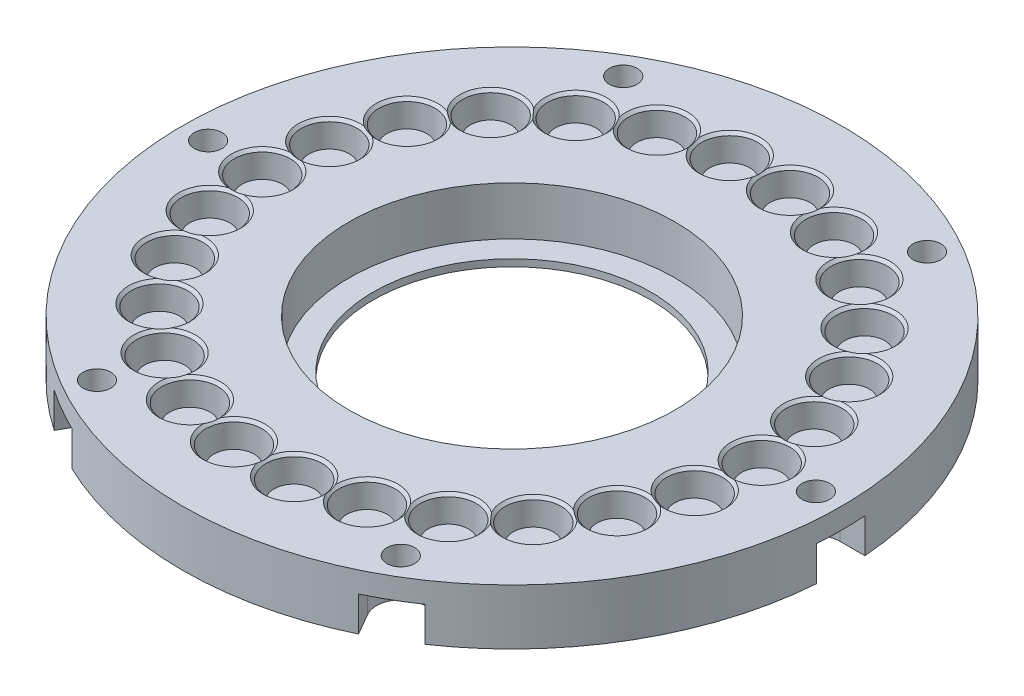
SolidWorks part; units mm, degrees
ref_plane "Front Plane" through (0, 0, 0) normal (0, 0, 1) x (1, 0, 0)
ref_plane "Top Plane" through (0, 0, 0) normal (0, 1, 0) x (1, 0, 0)
ref_plane "Right Plane" through (0, 0, 0) normal (1, 0, 0) x (0, 0, -1)
sketch "Sketch1" plane through (0, 0, 0) normal (0, 1, 0) x (1, 0, 0)
  circle A0 centre (0, 0) radius 47.5
  circle A1 centre (0, 0) radius 36 construction
  circle A2 centre (36, 0) radius 4.05
  circle A3 centre (34.9539, -8.6154) radius 4.05
  circle A4 centre (31.8764, -16.73) radius 4.05
  circle A5 centre (26.9464, -23.8724) radius 4.05
  circle A6 centre (20.4503, -29.6274) radius 4.05
  circle A7 centre (12.7658, -33.6606) radius 4.05
  circle A8 centre (4.3393, -35.7375) radius 4.05
  circle A9 centre (-4.3393, -35.7375) radius 4.05
  circle A10 centre (-12.7658, -33.6606) radius 4.05
  circle A11 centre (-20.4503, -29.6274) radius 4.05
  circle A12 centre (-26.9464, -23.8724) radius 4.05
  circle A13 centre (-31.8764, -16.73) radius 4.05
  circle A14 centre (-34.9539, -8.6154) radius 4.05
  circle A15 centre (-36, 0) radius 4.05
  circle A16 centre (-34.9539, 8.6154) radius 4.05
  circle A17 centre (-31.8764, 16.73) radius 4.05
  circle A18 centre (-26.9464, 23.8724) radius 4.05
  circle A19 centre (-20.4503, 29.6274) radius 4.05
  circle A20 centre (-12.7658, 33.6606) radius 4.05
  circle A21 centre (-4.3393, 35.7375) radius 4.05
  circle A22 centre (4.3393, 35.7375) radius 4.05
  circle A23 centre (12.7658, 33.6606) radius 4.05
  circle A24 centre (20.4503, 29.6274) radius 4.05
  circle A25 centre (26.9464, 23.8724) radius 4.05
  circle A26 centre (31.8764, 16.73) radius 4.05
  circle A27 centre (34.9539, 8.6154) radius 4.05
  point P58 (0, 0)
  dimension "D1" = 95
  dimension "D2" = 72
  dimension "D3" = 8.1
  dimension "D4" = 26
extrude "Boss-Extrude1" add sketch "Sketch1" along normal blind 5
sketch "Sketch2" plane through (0, 0, 0) normal (0, -1, 0) x (1, 0, 0)
  circle A1 centre (0, 0) radius 47.5
  circle A2 centre (0, 0) radius 47.5
  dimension "D1" = 0
extrude "Boss-Extrude2" add sketch "Sketch2" along normal blind 3
sketch "Sketch3" plane through (0, 0, 0) normal (0, 1, 0) x (1, 0, 0)
  circle A0 centre (36, 0) radius 2.9
  circle A1 centre (34.9539, -8.6154) radius 2.9
  circle A2 centre (31.8764, -16.73) radius 2.9
  circle A3 centre (26.9464, -23.8724) radius 2.9
  circle A4 centre (20.4503, -29.6274) radius 2.9
  circle A5 centre (12.7658, -33.6606) radius 2.9
  circle A6 centre (4.3393, -35.7375) radius 2.9
  circle A7 centre (-4.3393, -35.7375) radius 2.9
  circle A8 centre (-12.7658, -33.6606) radius 2.9
  circle A9 centre (-20.4503, -29.6274) radius 2.9
  circle A10 centre (-26.9464, -23.8724) radius 2.9
  circle A11 centre (-31.8764, -16.73) radius 2.9
  circle A12 centre (-34.9539, -8.6154) radius 2.9
  circle A13 centre (-36, 0) radius 2.9
  circle A14 centre (-34.9539, 8.6154) radius 2.9
  circle A15 centre (-31.8764, 16.73) radius 2.9
  circle A16 centre (-26.9464, 23.8724) radius 2.9
  circle A17 centre (-20.4503, 29.6274) radius 2.9
  circle A18 centre (-12.7658, 33.6606) radius 2.9
  circle A19 centre (-4.3393, 35.7375) radius 2.9
  circle A20 centre (4.3393, 35.7375) radius 2.9
  circle A21 centre (12.7658, 33.6606) radius 2.9
  circle A22 centre (20.4503, 29.6274) radius 2.9
  circle A23 centre (26.9464, 23.8724) radius 2.9
  circle A24 centre (31.8764, 16.73) radius 2.9
  circle A25 centre (34.9539, 8.6154) radius 2.9
  point P55 (0, 0)
  dimension "D1" = 5.8
  dimension "D2" = 26
extrude "Boss-Extrude3" add sketch "Sketch3" along normal blind 2
sketch "Sketch5" plane through (0, 5, 0) normal (0, 1, 0) x (1, 0, 0)
  circle A0 centre (0, 0) radius 23.5
  dimension "D1" = 47
extrude "Cut-Extrude2" cut sketch "Sketch5" against normal blind 7
sketch "Sketch6" plane through (0, -2, 0) normal (0, 1, 0) x (1, 0, 0)
  circle A2 centre (0, 0) radius 20
  circle A3 centre (0, 0) radius 20
  dimension "D1" = 3.5
extrude "Cut-Extrude3" cut sketch "Sketch6" against normal up to next contours A3
sketch "Sketch7" plane through (0, -3, 0) normal (0, -1, 0) x (1, 0, 0)
  line L0 (43.8, 3.5) -> (47.3709, 3.5)
  line L1 (43.8, -3.5) -> (47.3709, -3.5)
  line L2 (24.9311, -36.1819) -> (26.7165, -39.2744)
  line L3 (18.8689, -39.6819) -> (20.6543, -42.7744)
  line L4 (-18.8689, -39.6819) -> (-20.6543, -42.7744)
  line L5 (-24.9311, -36.1819) -> (-26.7165, -39.2744)
  line L6 (-43.8, -3.5) -> (-47.3709, -3.5)
  line L7 (-43.8, 3.5) -> (-47.3709, 3.5)
  line L8 (-24.9311, 36.1819) -> (-26.7165, 39.2744)
  line L9 (-18.8689, 39.6819) -> (-20.6543, 42.7744)
  line L10 (18.8689, 39.6819) -> (20.6543, 42.7744)
  line L11 (24.9311, 36.1819) -> (26.7165, 39.2744)
  circle A0 centre (0, 0) radius 43.8 construction
  arc A1 (43.8, 3.5) -> (43.8, -3.5) centre (43.8, 0) ccw
  circle A2 centre (0, 0) radius 47.5 construction
  circle A3 centre (0, 0) radius 47.5
  arc A4 (24.9311, -36.1819) -> (18.8689, -39.6819) centre (21.9, -37.9319) ccw
  arc A5 (-18.8689, -39.6819) -> (-24.9311, -36.1819) centre (-21.9, -37.9319) ccw
  arc A6 (-43.8, -3.5) -> (-43.8, 3.5) centre (-43.8, 0) ccw
  arc A7 (-24.9311, 36.1819) -> (-18.8689, 39.6819) centre (-21.9, 37.9319) ccw
  arc A8 (18.8689, 39.6819) -> (24.9311, 36.1819) centre (21.9, 37.9319) ccw
  point P38 (0, 0)
  circle M5 centre (0, 0) radius 47.5
  dimension "D1" = 87.6
  dimension "D2" = 7
  dimension "D3" = 6
extrude "Cut-Extrude4" cut sketch "Sketch7" against normal blind 5 contours L8 A7 L9 M5 | L6 A6 L7 M5 | L10 A8 L11 M5 | L0 A1 L1 M5 | L2 A4 L3 M5 | L4 A5 L5 M5 region at (44.2065, -3, 0) region at (22.1033, -3, 38.284) region at (22.1033, -3, -38.284) region at (-22.1033, -3, 38.284) region at (-22.1033, -3, -38.284) region at (-44.2065, -3, 0)
sketch "Sketch8" plane through (0, 2, 0) normal (0, -1, 0) x (1, 0, 0)
  circle A0 centre (43.8, 0) radius 2
  circle A1 centre (21.9, -37.9319) radius 2
  circle A2 centre (-21.9, -37.9319) radius 2
  circle A3 centre (-43.8, 0) radius 2
  circle A4 centre (-21.9, 37.9319) radius 2
  circle A5 centre (21.9, 37.9319) radius 2
  point P16 (0, 0)
  dimension "D1" = 4
  dimension "D2" = 6
extrude "Cut-Extrude5" cut sketch "Sketch8" against normal through all
chamfer "Chamfer1" distance 0.4 angle 45 27 edges at (-20.4503, 5, -25.5774) (4.3393, 0, 39.7875) (4.3393, 5, 39.7875) (-26.9464, 5, -19.8224) (-31.8764, 5, -12.68) (-34.9539, 5, -4.5654) (-36, 5, 4.05) (-34.9539, 5, 12.6654) (-31.8764, 5, 20.78) (-26.9464, 5, 27.9224) (-20.4503, 5, 33.6774) (-12.7658, 5, 37.7106) (-4.3393, 5, 39.7875) (12.7658, 5, 37.7106) (20.4503, 5, 33.6774) (26.9464, 5, 27.9224) (31.8764, 5, 20.78) (34.9539, 5, 12.6654) (36, 5, 4.05) (34.9539, 5, -4.5654) (31.8764, 5, -12.68) (26.9464, 5, -19.8224) (20.4503, 5, -25.5774) (12.7658, 5, -29.6106) (4.3393, 5, -31.6875) (-4.3393, 5, -31.6875) (-12.7658, 5, -29.6106)
